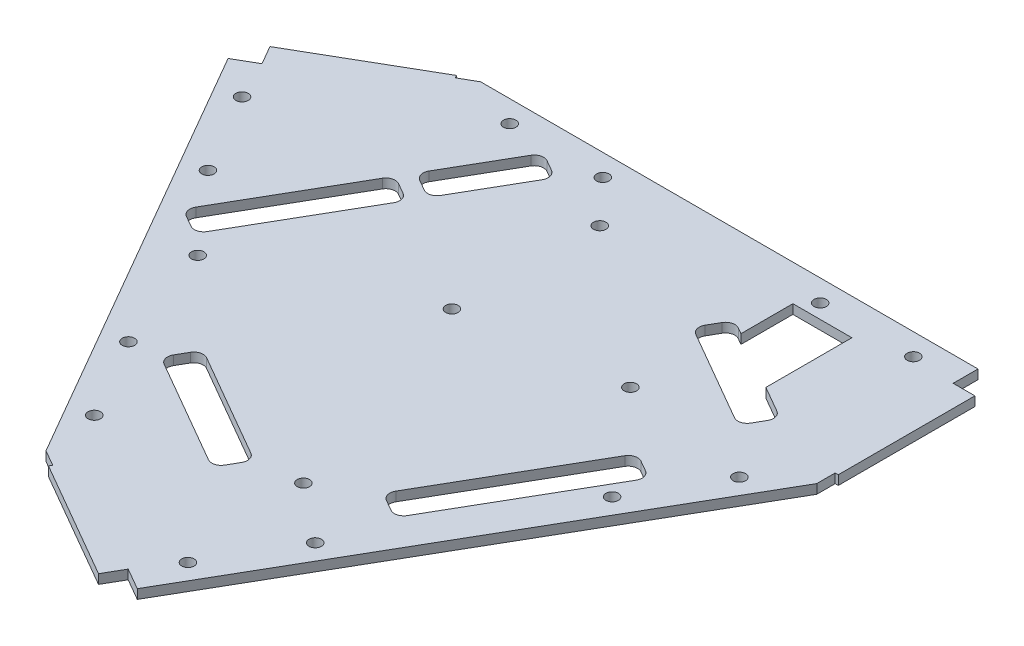
SolidWorks part; units mm, degrees
material "PVC rigide"
ref_plane "Plan de face" through (0, 0, 0) normal (0, 0, 1) x (1, 0, 0)
ref_plane "Plan de dessus" through (0, 0, 0) normal (0, 1, 0) x (1, 0, 0)
ref_plane "Plan de droite" through (0, 0, 0) normal (1, 0, 0) x (0, 0, -1)
sketch "Esquisse1" plane through (0, 0, 0) normal (0, 1, 0) x (1, 0, 0)
  line L0 (-64.1795, 79.9408) -> (98.8205, 79.9408)
  line L6 (-118.641, 45.6107) -> (-37.141, -95.5515)
  line L7 (19.8205, -125.5515) -> (101.3205, 15.6107)
  line L8 (-73.5096, 77.4408) -> (-116.8109, 52.4408)
  line L9 (103.8205, 74.9408) -> (103.8205, 24.9408)
  line L10 (12.9904, -127.3816) -> (-30.3109, -102.3816)
  line L11 (-69.1795, 79.9408) -> (-138.4615, 79.9408) construction
  line L12 (-121.141, 49.9408) -> (-138.4615, 79.9408) construction
  line L13 (-34.641, -99.8816) -> (0, -159.8816) construction
  line L14 (17.3205, -129.8816) -> (0, -159.8816) construction
  line L15 (103.8205, 79.9408) -> (138.4615, 79.9408) construction
  line L16 (103.8205, 19.9408) -> (138.4615, 79.9408) construction
  line L17 (0, -159.8816) -> (0, 79.9408) construction
  line L18 (-138.4615, 79.9408) -> (69.2308, -39.9704) construction
  line L19 (-69.2308, -39.9704) -> (138.4615, 79.9408) construction
  line L20 (12.9904, -127.3816) -> (19.8205, -125.5515)
  line L21 (17.3205, -129.8816) -> (19.8205, -125.5515) construction
  line L22 (-121.141, 49.9408) -> (-118.641, 45.6107) construction
  line L23 (-116.8109, 52.4408) -> (-118.641, 45.6107)
  line L24 (103.8205, 79.9408) -> (98.8205, 79.9408) construction
  line L25 (103.8205, 74.9408) -> (98.8205, 79.9408)
  line L26 (-30.3109, -102.3816) -> (-37.141, -95.5515)
  line L27 (-34.641, -99.8816) -> (-37.141, -95.5515) construction
  line L28 (-30.3109, -102.3816) -> (-34.641, -99.8816) construction
  line L29 (-73.5096, 77.4408) -> (-69.1795, 79.9408) construction
  line L30 (-69.1795, 79.9408) -> (-64.1795, 79.9408) construction
  line L31 (-73.5096, 77.4408) -> (-64.1795, 79.9408)
  line L32 (103.8205, 24.9408) -> (103.8205, 19.9408) construction
  line L33 (103.8205, 19.9408) -> (101.3205, 15.6107) construction
  line L34 (103.8205, 24.9408) -> (101.3205, 15.6107)
  point P12 (0, 0)
  point P24 (0, 0)
  point P34 (0, 0)
  dimension "D1" = 90
  dimension "D2" = 90
  dimension "D3" = 90
  dimension "D4" = 173
  dimension "D5" = 60
  dimension "D6" = 5
  dimension "D7" = 5
  dimension "D9" = 5
  dimension "D10" = 5
  dimension "D8" = 3
  dimension "D11" = 3
extrude "Extrusion1" add sketch "Esquisse1" along normal blind 3
sketch "Esquisse8" plane through (0, 3, 0) normal (0, 1, 0) x (1, 0, 0)
  line L0 (-116.7713, 62.3721) -> (15.6302, -166.954) construction
  line L1 (-118.641, 45.6107) -> (-37.141, -95.5515) construction
  line L2 (-60.5705, -34.9704) -> (0, 0) construction
  line L3 (-69.2308, -39.9704) -> (138.4615, 79.9408) construction
  circle A0 centre (-100.5705, 34.3116) radius 2
  circle A1 centre (80, 69.9408) radius 2
  circle A2 centre (50, 69.9408) radius 2
  circle A3 centre (-50.5705, -52.2909) radius 2
  circle A4 centre (-35.5705, -78.2717) radius 2
  circle A5 centre (-20, 69.9408) radius 2
  circle A6 centre (-50, 69.9408) radius 2
  circle A7 centre (20.5705, -104.2524) radius 2
  circle A8 centre (35.5705, -78.2717) radius 2
  circle A9 centre (-85.5705, 8.3309) radius 2
  circle A10 centre (70.5705, -17.6499) radius 2
  circle A11 centre (85.5705, 8.3309) radius 2
  point P29 (0, 0)
  point P36 (0, 0)
  point P77 (0, 0)
  dimension "D2" = 4
  dimension "D4" = 70
  dimension "D1" = 10
  dimension "D3" = 30
  dimension "D5" = 30
  dimension "D6" = 3
  dimension "D7" = 50
extrude "Enlèv. mat.-Extru.14" cut sketch "Esquisse8" against normal up to next
sketch "Esquisse10" plane through (0, 3, 0) normal (0, 1, 0) x (1, 0, 0)
  line L0 (-68.3013, -18.3013) -> (18.3013, -68.3013) construction
  line L2 (-68.3013, -18.3013) -> (-18.3013, 68.3013) construction
  line L3 (-18.3013, 68.3013) -> (68.3013, 18.3013) construction
  line L4 (68.3013, 18.3013) -> (18.3013, -68.3013) construction
  line L6 (-68.3013, -18.3013) -> (68.3013, 18.3013) construction
  line L7 (-18.3013, 68.3013) -> (18.3013, -68.3013) construction
  line L8 (19.8205, -125.5515) -> (101.3205, 15.6107) construction
  circle A0 centre (-63.5202, -17.0202) radius 2
  circle A1 centre (17.0202, -63.5202) radius 2
  circle A2 centre (42.9659, 15.8391) radius 2
  circle A3 centre (-7.6292, 8.9658) radius 2
  circle A4 centre (-7.0291, 55.9852) radius 2
  point P16 (0, 0)
  dimension "D2" = 4
  dimension "D5" = 3.5
  dimension "D10" = 38.91
  dimension "D12" = 5.03
  dimension "D1" = 100
  dimension "D3" = 3.5
  dimension "D4" = 3.5
  dimension "D6" = 3.5
  dimension "D7" = 20.71
  dimension "D8" = 14.8
  dimension "D9" = 46.05
  dimension "D11" = 15.92
extrude "Enlèv. mat.-Extru.16" cut sketch "Esquisse10" against normal through all
sketch "Esquisse12" plane through (0, 3, 0) normal (0, 1, 0) x (1, 0, 0)
  line L0 (-65.9775, 76.9408) -> (93.8205, 76.9408)
  line L1 (-65.9775, 76.9408) -> (-66.3756, 76.9408)
  line L2 (-72.0096, 74.8427) -> (-71.5096, 73.9767)
  line L3 (-71.5096, 73.9767) -> (-66.3756, 76.9408)
  line L4 (99.6214, 18.6677) -> (19.7224, -119.7213)
  line L5 (93.8205, 79.9408) -> (-64.1795, 79.9408)
  line L6 (-64.1795, 79.9408) -> (-73.5096, 77.4408)
  line L7 (-72.0096, 74.8427) -> (-110.1147, 52.8427)
  line L9 (-72.0096, 74.8427) -> (-115.3109, 49.8427) construction
  line L11 (-73.5096, 77.4408) -> (-116.8109, 52.4408)
  line L12 (-116.8109, 52.4408) -> (-117.909, 48.3427)
  line L13 (-116.8109, 52.4408) -> (-118.641, 45.6107) construction
  line L14 (-110.1147, 52.8427) -> (-106.6147, 46.7805)
  line L17 (-113.5429, 42.7805) -> (-106.6147, 46.7805)
  line L18 (99.6214, 18.6677) -> (99.8205, 19.0126)
  line L19 (100.8205, 24.9408) -> (99.8205, 24.9408)
  line L20 (99.8205, 24.9408) -> (99.8205, 19.0126)
  line L21 (22.3205, -121.2213) -> (101.3205, 15.6107)
  line L22 (101.3205, 15.6107) -> (103.8205, 24.9408)
  line L23 (100.8205, 24.9408) -> (100.8205, 68.9408)
  line L24 (103.8205, 24.9408) -> (103.8205, 74.9408)
  line L25 (103.8205, 74.9408) -> (100.8205, 77.9408)
  line L26 (100.8205, 68.9408) -> (93.8205, 68.9408)
  line L27 (93.8205, 76.9408) -> (93.8205, 68.9408)
  line L28 (-33.644, -95.6085) -> (-113.5429, 42.7805)
  line L29 (-33.644, -95.6085) -> (-33.4449, -95.9534)
  line L30 (-28.8109, -99.7835) -> (-28.3109, -98.9175)
  line L31 (-28.3109, -98.9175) -> (-33.4449, -95.9534)
  line L32 (-116.141, 41.2805) -> (-37.141, -95.5515)
  line L33 (-37.141, -95.5515) -> (-30.3109, -102.3816)
  line L34 (-28.8109, -99.7835) -> (9.2942, -121.7835)
  line L35 (-30.3109, -102.3816) -> (12.9904, -127.3816)
  line L36 (12.9904, -127.3816) -> (17.0885, -126.2835)
  line L37 (9.2942, -121.7835) -> (12.7942, -115.7213)
  line L38 (19.7224, -119.7213) -> (12.7942, -115.7213)
  point P59 (0, 0)
  line M20 (12.9904, -127.3816) -> (19.8205, -125.5515)
  line M21 (19.8205, -125.5515) -> (101.3205, 15.6107)
  line M22 (101.3205, 15.6107) -> (103.8205, 24.9408)
  line M23 (103.8205, 24.9408) -> (103.8205, 74.9408)
  line M24 (103.8205, 74.9408) -> (98.8205, 79.9408)
  line M25 (98.8205, 79.9408) -> (-64.1795, 79.9408)
  line M26 (-64.1795, 79.9408) -> (-73.5096, 77.4408)
  line M27 (-73.5096, 77.4408) -> (-116.8109, 52.4408)
  line M28 (-116.8109, 52.4408) -> (-118.641, 45.6107)
  line M29 (-118.641, 45.6107) -> (-37.141, -95.5515)
  line M30 (-37.141, -95.5515) -> (-30.3109, -102.3816)
  line M31 (-30.3109, -102.3816) -> (12.9904, -127.3816)
  dimension "D1" = 3
extrude "Enlèv. mat.-Extru.17" cut sketch "Esquisse12" against normal through all contours L4 L38 L37 L34 L30 L31 L29 L28 L17 L14 L7 L2 L3 L1 L0 L27 L26 L23 L19 L20 L18 M31 M20 M21 M22 M23 M24 M25 M26 M27 M28 M29 M30 region at (96.3205, 3, -76.8999)
sketch "Esquisse13" plane through (0, 3, 0) normal (0, 1, 0) x (1, 0, 0)
  line L0 (-70.1314, -11.4711) -> (-45.1314, 31.8301)
  line L1 (-68.3013, -18.3013) -> (-18.3013, 68.3013) construction
  line L2 (-45.1314, 31.8301) -> (-53.7917, 36.8301)
  line L3 (-53.7917, 36.8301) -> (-78.7917, -6.4711)
  line L4 (-78.7917, -6.4711) -> (-70.1314, -11.4711)
  line L5 (-68.3013, -18.3013) -> (18.3013, -68.3013) construction
  line L7 (-51.2917, 41.1603) -> (-36.2917, 67.141)
  line L8 (-36.2917, 67.141) -> (-27.6314, 62.141)
  line L9 (-27.6314, 62.141) -> (-42.6314, 36.1603)
  line L10 (-42.6314, 36.1603) -> (-51.2917, 41.1603)
  line L11 (32.6314, -53.4808) -> (62.6314, -1.5192)
  line L12 (62.6314, -1.5192) -> (71.2917, -6.5192)
  line L13 (71.2917, -6.5192) -> (41.2917, -58.4808)
  line L14 (41.2917, -58.4808) -> (32.6314, -53.4808)
  line L15 (68.3013, 18.3013) -> (18.3013, -68.3013) construction
  line L16 (70.8013, 22.6314) -> (36.1603, 42.6314)
  line L17 (36.1603, 42.6314) -> (41.1603, 51.2917)
  line L18 (41.1603, 51.2917) -> (45.8039, 48.6107)
  line L19 (75.8013, 31.2917) -> (70.8013, 22.6314)
  line L20 (-18.3013, 68.3013) -> (68.3013, 18.3013) construction
  line L21 (2.8109, -65.1314) -> (-36.1603, -42.6314)
  line L22 (-36.1603, -42.6314) -> (-41.1603, -51.2917)
  line L23 (-41.1603, -51.2917) -> (-2.1891, -73.7917)
  line L24 (-2.1891, -73.7917) -> (2.8109, -65.1314)
  line L25 (64.8039, 37.641) -> (75.8013, 31.2917)
  line L26 (45.8039, 65.3424) -> (64.8039, 65.3424)
  line L27 (45.8039, 65.3424) -> (45.8039, 48.6107)
  line L29 (64.8039, 65.3424) -> (64.8039, 46.3424)
  line L30 (45.8039, 65.3424) -> (64.8039, 46.3424) construction
  line L31 (47.2419, 47.7804) -> (64.8039, 65.3424) construction
  line L32 (64.8039, 46.3424) -> (64.8039, 37.641)
  point P35 (55.3039, 55.8424)
  dimension "D5" = 30
  dimension "D1" = 50
  dimension "D2" = 10
  dimension "D3" = 5
  dimension "D4" = 5
  dimension "D6" = 5
  dimension "D7" = 10
  dimension "D8" = 5
  dimension "D9" = 20
  dimension "D10" = 60
  dimension "D11" = 5
  dimension "D12" = 10
  dimension "D13" = 40
  dimension "D14" = 15
  dimension "D15" = 45
  dimension "D16" = 5
  dimension "D17" = 10
  dimension "D19" = 19
extrude "Enlèv. mat.-Extru.18" cut sketch "Esquisse13" against normal through all
fillet "Congé1" radius 3 20 edges at (-41.1603, 1.5, 51.2917) (-36.1603, 1.5, 42.6314) (2.8109, 1.5, 65.1314) (-2.1891, 1.5, 73.7917) (32.6314, 1.5, 53.4808) (41.2917, 1.5, 58.4808) (62.6314, 1.5, 1.5192) (71.2917, 1.5, 6.5192) (36.1603, 1.5, -42.6314) (70.8013, 1.5, -22.6314) (41.1603, 1.5, -51.2917) (-36.2917, 1.5, -67.141) (-27.6314, 1.5, -62.141) (-51.2917, 1.5, -41.1603) (-42.6314, 1.5, -36.1603) (-70.1314, 1.5, 11.4711) (-45.1314, 1.5, -31.8301) (-78.7917, 1.5, 6.4711) (-53.7917, 1.5, -36.8301) (75.8013, 1.5, -31.2917)
